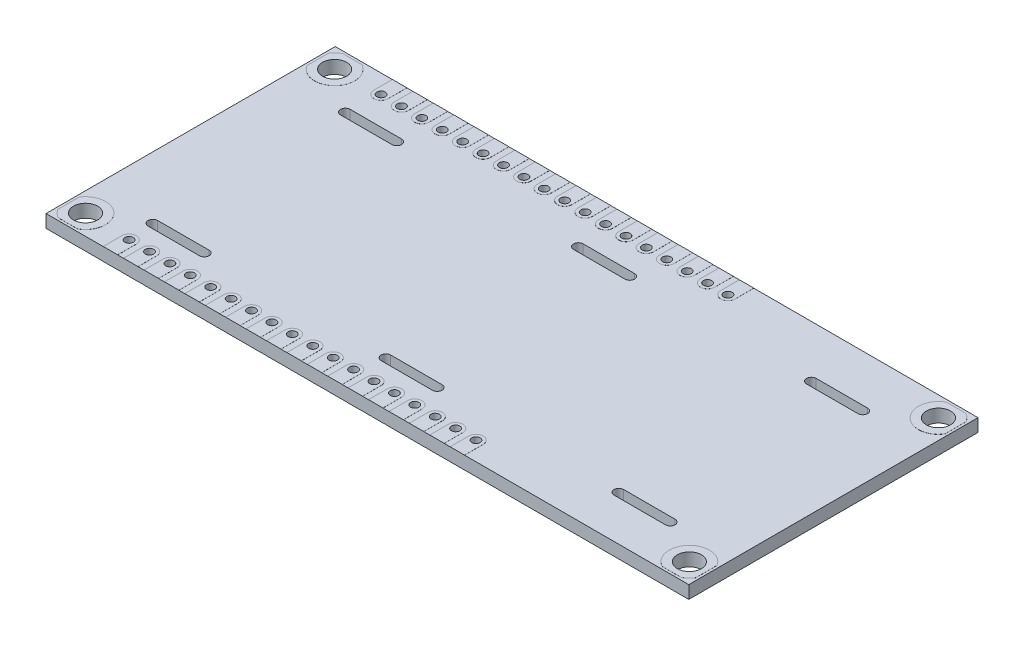
SolidWorks part; units mm, degrees
ref_plane "Plan de face" through (0, 0, 0) normal (0, 0, 1) x (1, 0, 0)
ref_plane "Plan de dessus" through (0, 0, 0) normal (0, 1, 0) x (1, 0, 0)
ref_plane "Plan de droite" through (0, 0, 0) normal (1, 0, 0) x (0, 0, -1)
sketch "Esquisse1" plane through (0, 0, 0) normal (0, 1, 0) x (1, 0, 0)
  line L0 (40, 36) -> (40, 28.6716) construction
  line L1 (0, 0) -> (80, 0)
  line L2 (0, 0) -> (0, 36)
  line L3 (0, 36) -> (80, 36)
  line L4 (80, 0) -> (80, 36)
  line L5 (0, 18) -> (8.7916, 18) construction
  line L6 (-3.0961, 33.68) -> (82.0612, 33.68) construction
  line L7 (7.7, 30.16) -> (14.1, 30.16)
  line L8 (7.7, 6.2) -> (14.1, 6.2)
  line L9 (7.7, 28.96) -> (14.1, 28.96)
  line L10 (7.7, 5) -> (14.1, 5)
  line L11 (36.7, 30.16) -> (43.1, 30.16)
  line L12 (36.7, 28.96) -> (43.1, 28.96)
  line L13 (36.7, 6.2) -> (43.1, 6.2)
  line L14 (36.7, 5) -> (43.1, 5)
  line L15 (65.7, 30.16) -> (72.1, 30.16)
  line L16 (65.7, 28.96) -> (72.1, 28.96)
  line L17 (65.7, 6.2) -> (72.1, 6.2)
  line L18 (65.7, 5) -> (72.1, 5)
  line L19 (72.3, 41.4898) -> (72.3, -1.3318) construction
  circle A0 centre (2.42, 33.5) radius 1.5
  circle A1 centre (2.42, 2.5) radius 1.5
  circle A2 centre (77.58, 2.5) radius 1.5
  circle A3 centre (77.58, 33.5) radius 1.5
  circle A4 centre (8.02, 33.68) radius 0.52
  circle A5 centre (10.56, 33.68) radius 0.52
  circle A6 centre (13.1, 33.68) radius 0.52
  circle A7 centre (15.64, 33.68) radius 0.52
  circle A8 centre (18.18, 33.68) radius 0.52
  circle A9 centre (20.72, 33.68) radius 0.52
  circle A10 centre (23.26, 33.68) radius 0.52
  circle A11 centre (25.8, 33.68) radius 0.52
  circle A12 centre (28.34, 33.68) radius 0.52
  circle A13 centre (30.88, 33.68) radius 0.52
  circle A14 centre (33.42, 33.68) radius 0.52
  circle A15 centre (35.96, 33.68) radius 0.52
  circle A16 centre (38.5, 33.68) radius 0.52
  circle A17 centre (41.04, 33.68) radius 0.52
  circle A18 centre (43.58, 33.68) radius 0.52
  circle A19 centre (46.12, 33.68) radius 0.52
  arc A20 (7.7, 6.2) -> (7.7, 5) centre (7.7, 5.6) ccw
  arc A21 (14.1, 5) -> (14.1, 6.2) centre (14.1, 5.6) ccw
  arc A22 (7.7, 30.16) -> (7.7, 28.96) centre (7.7, 29.56) ccw
  arc A23 (14.1, 28.96) -> (14.1, 30.16) centre (14.1, 29.56) ccw
  arc A24 (36.7, 30.16) -> (36.7, 28.96) centre (36.7, 29.56) ccw
  arc A25 (43.1, 28.96) -> (43.1, 30.16) centre (43.1, 29.56) ccw
  arc A26 (36.7, 6.2) -> (36.7, 5) centre (36.7, 5.6) ccw
  arc A27 (43.1, 5) -> (43.1, 6.2) centre (43.1, 5.6) ccw
  arc A28 (65.7, 30.16) -> (65.7, 28.96) centre (65.7, 29.56) ccw
  arc A29 (72.1, 28.96) -> (72.1, 30.16) centre (72.1, 29.56) ccw
  arc A30 (65.7, 6.2) -> (65.7, 5) centre (65.7, 5.6) ccw
  arc A31 (72.1, 5) -> (72.1, 6.2) centre (72.1, 5.6) ccw
  circle A32 centre (48.66, 33.68) radius 0.52
  circle A33 centre (51.2, 33.68) radius 0.52
  circle A34 centre (51.2, 2.32) radius 0.52
  circle A35 centre (48.66, 2.32) radius 0.52
  circle A36 centre (46.12, 2.32) radius 0.52
  circle A37 centre (41.04, 2.32) radius 0.52
  circle A38 centre (43.58, 2.32) radius 0.52
  circle A39 centre (38.5, 2.32) radius 0.52
  circle A40 centre (35.96, 2.32) radius 0.52
  circle A41 centre (33.42, 2.32) radius 0.52
  circle A42 centre (30.88, 2.32) radius 0.52
  circle A43 centre (28.34, 2.32) radius 0.52
  circle A44 centre (25.8, 2.32) radius 0.52
  circle A45 centre (23.26, 2.32) radius 0.52
  circle A46 centre (20.72, 2.32) radius 0.52
  circle A47 centre (18.18, 2.32) radius 0.52
  circle A48 centre (15.64, 2.32) radius 0.52
  circle A49 centre (13.1, 2.32) radius 0.52
  circle A50 centre (10.56, 2.32) radius 0.52
  circle A51 centre (8.02, 2.32) radius 0.52
  dimension "D3" = 3
  dimension "D8" = 1.04
  dimension "D10" = 1.2
  dimension "D16" = 0.6
  dimension "D18" = 1.04
  dimension "D20" = 1.04
  dimension "D1" = 80
  dimension "D2" = 36
  dimension "D4" = 31
  dimension "D5" = 75.16
  dimension "D6" = 2.32
  dimension "D7" = 8.02
  dimension "D11" = 6.4
  dimension "D12" = 5
  dimension "D13" = 7.7
  dimension "D14" = 5.84
  dimension "D15" = 7.7
  dimension "D17" = 3
  dimension "D19" = 2.54
  dimension "D21" = 2.54
  dimension "D9" = 16
extrude "Boss.-Extru.1" add sketch "Esquisse1" along normal blind 1.6
sketch "Esquisse2" plane through (0, 1.6, 0) normal (0, 1, 0) x (1, 0, 0)
  line L0 (80, 36) -> (0, 36) construction
  line L1 (0.3, 32.175) -> (0.3, 34.825)
  line L2 (7.12, 33.68) -> (7.12, 36)
  line L3 (7.12, 36) -> (8.92, 36)
  line L4 (8.92, 33.68) -> (8.92, 36)
  line L5 (3.6074, 0.3) -> (1.2326, 0.3)
  line L6 (0.3, 1.175) -> (0.3, 3.825)
  line L7 (0, 36) -> (0, 0) construction
  line L8 (0, 0) -> (80, 0) construction
  line L9 (1.2326, 35.7) -> (3.6074, 35.7)
  line L10 (76.3926, 0.3) -> (78.7674, 0.3)
  line L11 (79.7, 1.175) -> (79.7, 3.825)
  line L12 (80, 0) -> (80, 36) construction
  line L13 (79.7, 32.175) -> (79.7, 34.825)
  line L14 (78.7674, 35.7) -> (76.3926, 35.7)
  line L15 (9.66, 33.68) -> (9.66, 36)
  line L16 (9.66, 36) -> (11.46, 36)
  line L17 (11.46, 33.68) -> (11.46, 36)
  line L18 (12.2, 33.68) -> (12.2, 36)
  line L19 (12.2, 36) -> (14, 36)
  line L20 (14, 33.68) -> (14, 36)
  line L21 (14.74, 33.68) -> (14.74, 36)
  line L22 (14.74, 36) -> (16.54, 36)
  line L23 (16.54, 33.68) -> (16.54, 36)
  line L24 (17.28, 33.68) -> (17.28, 36)
  line L25 (17.28, 36) -> (19.08, 36)
  line L26 (19.08, 33.68) -> (19.08, 36)
  line L27 (19.82, 33.68) -> (19.82, 36)
  line L28 (19.82, 36) -> (21.62, 36)
  line L29 (21.62, 33.68) -> (21.62, 36)
  line L30 (22.36, 33.68) -> (22.36, 36)
  line L31 (22.36, 36) -> (24.16, 36)
  line L32 (24.16, 33.68) -> (24.16, 36)
  line L33 (24.9, 33.68) -> (24.9, 36)
  line L34 (24.9, 36) -> (26.7, 36)
  line L35 (26.7, 33.68) -> (26.7, 36)
  line L36 (27.44, 33.68) -> (27.44, 36)
  line L37 (27.44, 36) -> (29.24, 36)
  line L38 (29.24, 33.68) -> (29.24, 36)
  line L39 (29.98, 33.68) -> (29.98, 36)
  line L40 (29.98, 36) -> (31.78, 36)
  line L41 (31.78, 33.68) -> (31.78, 36)
  line L42 (32.52, 33.68) -> (32.52, 36)
  line L43 (32.52, 36) -> (34.32, 36)
  line L44 (34.32, 33.68) -> (34.32, 36)
  line L45 (35.06, 33.68) -> (35.06, 36)
  line L46 (35.06, 36) -> (36.86, 36)
  line L47 (36.86, 33.68) -> (36.86, 36)
  line L48 (37.6, 33.68) -> (37.6, 36)
  line L49 (37.6, 36) -> (39.4, 36)
  line L50 (39.4, 33.68) -> (39.4, 36)
  line L51 (40.14, 33.68) -> (40.14, 36)
  line L52 (40.14, 36) -> (41.94, 36)
  line L53 (41.94, 33.68) -> (41.94, 36)
  line L54 (42.68, 33.68) -> (42.68, 36)
  line L55 (42.68, 36) -> (44.48, 36)
  line L56 (44.48, 33.68) -> (44.48, 36)
  line L57 (45.22, 33.68) -> (45.22, 36)
  line L58 (45.22, 36) -> (47.02, 36)
  line L59 (47.02, 33.68) -> (47.02, 36)
  line L60 (47.76, 33.68) -> (47.76, 36)
  line L61 (47.76, 36) -> (49.56, 36)
  line L62 (49.56, 33.68) -> (49.56, 36)
  line L63 (50.3, 33.68) -> (50.3, 36)
  line L64 (50.3, 36) -> (52.1, 36)
  line L65 (52.1, 33.68) -> (52.1, 36)
  arc A0 (3.6074, 0.3) -> (0.3, 3.825) centre (2.42, 2.5) ccw
  arc A1 (0.3, 32.175) -> (3.6074, 35.7) centre (2.42, 33.5) ccw
  arc A2 (76.3926, 35.7) -> (79.7, 32.175) centre (77.58, 33.5) ccw
  arc A3 (78.7674, 0.3) -> (79.7, 1.175) centre (77.58, 2.5) ccw
  arc A4 (7.12, 33.68) -> (8.92, 33.68) centre (8.02, 33.68) ccw
  circle A5 centre (8.02, 33.68) radius 0.52
  arc A6 (1.2326, 35.7) -> (0.3, 34.825) centre (2.42, 33.5) ccw
  arc A7 (0.3, 1.175) -> (1.2326, 0.3) centre (2.42, 2.5) ccw
  arc A8 (79.7, 3.825) -> (76.3926, 0.3) centre (77.58, 2.5) ccw
  arc A9 (79.7, 34.825) -> (78.7674, 35.7) centre (77.58, 33.5) ccw
  arc A10 (9.66, 33.68) -> (11.46, 33.68) centre (10.56, 33.68) ccw
  circle A11 centre (10.56, 33.68) radius 0.52
  arc A12 (12.2, 33.68) -> (14, 33.68) centre (13.1, 33.68) ccw
  circle A13 centre (13.1, 33.68) radius 0.52
  arc A14 (14.74, 33.68) -> (16.54, 33.68) centre (15.64, 33.68) ccw
  circle A15 centre (15.64, 33.68) radius 0.52
  arc A16 (17.28, 33.68) -> (19.08, 33.68) centre (18.18, 33.68) ccw
  circle A17 centre (18.18, 33.68) radius 0.52
  arc A18 (19.82, 33.68) -> (21.62, 33.68) centre (20.72, 33.68) ccw
  circle A19 centre (20.72, 33.68) radius 0.52
  arc A20 (22.36, 33.68) -> (24.16, 33.68) centre (23.26, 33.68) ccw
  circle A21 centre (23.26, 33.68) radius 0.52
  arc A22 (24.9, 33.68) -> (26.7, 33.68) centre (25.8, 33.68) ccw
  circle A23 centre (25.8, 33.68) radius 0.52
  arc A24 (27.44, 33.68) -> (29.24, 33.68) centre (28.34, 33.68) ccw
  circle A25 centre (28.34, 33.68) radius 0.52
  arc A26 (29.98, 33.68) -> (31.78, 33.68) centre (30.88, 33.68) ccw
  circle A27 centre (30.88, 33.68) radius 0.52
  arc A28 (32.52, 33.68) -> (34.32, 33.68) centre (33.42, 33.68) ccw
  circle A29 centre (33.42, 33.68) radius 0.52
  arc A30 (35.06, 33.68) -> (36.86, 33.68) centre (35.96, 33.68) ccw
  circle A31 centre (35.96, 33.68) radius 0.52
  arc A32 (37.6, 33.68) -> (39.4, 33.68) centre (38.5, 33.68) ccw
  circle A33 centre (38.5, 33.68) radius 0.52
  arc A34 (40.14, 33.68) -> (41.94, 33.68) centre (41.04, 33.68) ccw
  circle A35 centre (41.04, 33.68) radius 0.52
  arc A36 (42.68, 33.68) -> (44.48, 33.68) centre (43.58, 33.68) ccw
  circle A37 centre (43.58, 33.68) radius 0.52
  arc A38 (45.22, 33.68) -> (47.02, 33.68) centre (46.12, 33.68) ccw
  circle A39 centre (46.12, 33.68) radius 0.52
  circle A40 centre (2.42, 33.5) radius 1.5
  circle A41 centre (2.42, 2.5) radius 1.5
  circle A42 centre (77.58, 2.5) radius 1.5
  circle A43 centre (77.58, 33.5) radius 1.5
  arc A44 (47.76, 33.68) -> (49.56, 33.68) centre (48.66, 33.68) ccw
  circle A45 centre (48.66, 33.68) radius 0.52
  circle A46 centre (48.66, 33.68) radius 0.52 construction
  arc A47 (50.3, 33.68) -> (52.1, 33.68) centre (51.2, 33.68) ccw
  circle A48 centre (51.2, 33.68) radius 0.52
  circle A49 centre (51.2, 33.68) radius 0.52 construction
  dimension "D1" = 1.8
  dimension "D2" = 5
  dimension "D5" = 5
  dimension "D8" = 5
  dimension "D11" = 5
  dimension "D3" = 0.3
  dimension "D4" = 0.3
  dimension "D6" = 0.3
  dimension "D7" = 0.3
  dimension "D9" = 0.3
  dimension "D10" = 0.3
  dimension "D12" = 0.3
  dimension "D13" = 0.3
  dimension "D14" = 16
extrude "Boss.-Extru.2" add sketch "Esquisse2" along normal blind 0.01
extrude "Boss.-Extru.3" add sketch "Esquisse2<2>" against normal blind 0.01 from surface starting at face at (10.56, 0, -2.84)
sketch "Esquisse2<2>" plane through (0, 1.6, 0) normal (0, 1, 0) x (1, 0, 0) same geometry as "Esquisse2"
ref_plane "Plan1" through (0, 0, -18) normal (0, 0, -1) x (-1, 0, 0)
sketch "Esquisse3" plane through (0, 0, -18) normal (0, 0, -1) x (-1, 0, 0)
  line L0 (-27.5, 0) -> (-27.5, -12.0338) construction
  line L1 (-27.5, -12.0338) -> (-54, -12.0338) construction
  line L2 (-54, -12.0338) -> (-54, 0) construction
  line L3 (-37.6, 0) -> (-36.86, 0) construction
  line L4 (0, 1.6) -> (0, 0) construction
  line L5 (-62.9183, -1.2) -> (-16.9793, -1.2) construction
  line L6 (-80, 0) -> (-52.1, 0) construction
  line L7 (-67.9847, 0) -> (-4.6388, 0) construction
  line L8 (-59.75, 8.5335) -> (-59.75, -8.5682) construction
  line L9 (-20.75, 7.9666) -> (-20.75, -6.8674) construction
  line L10 (-48.25, 8.5335) -> (-48.25, -15.2765) construction
  line L11 (-34.25, 7.9666) -> (-34.25, -8.5682) construction
  line L12 (-20.75, 0) -> (-27.5, 0)
  line L13 (-27.5, 0) -> (-27.5, -1.2)
  line L14 (-54, 0) -> (-54, -1.2)
  line L15 (-54, 0) -> (-48.25, 0)
  arc A0 (-59.79, 0) -> (-59.75, -0.0173) centre (-54.02, 13.272) ccw
  arc A1 (-27.5, -1.2) -> (-20.75, 0) centre (-27.5, 18.3844) ccw
  arc A2 (-54, -1.2) -> (-48.25, 0) centre (-54.02, 13.272) ccw
  point P2 (0, 0.8)
  point P24 (-59.75, -0.0173)
  point P25 (-48.25, 0)
  point P26 (-54, -1.2)
  point P29 (-34.25, 0)
  point P30 (-20.75, 0)
  point P31 (-27.5, -1.2)
  dimension "D1" = 26.5
  dimension "D2" = 27.5
  dimension "D3" = 1.2
  dimension "D4" = 5.75
  dimension "D5" = 5.75
  dimension "D6" = 6.75
  dimension "D7" = 6.75
revolve "Révolution1" add sketch "Esquisse3" angle 360 about L2 region at (51.8325, -0.4811, -18)
revolve "Révolution2" add sketch "Esquisse3<6>" angle 360 about L0 region at (24.9581, -0.4813, -18)
sketch "Esquisse3<6>" plane through (0, 0, -18) normal (0, 0, -1) x (-1, 0, 0) same geometry as "Esquisse3"
mirror "Mirror1" about plane through (0, 0, -18) normal (0, 0, -1) of "Boss.-Extru.2"
mirror "Mirror2" about plane through (0, 0, -18) normal (0, 0, -1) of "Boss.-Extru.3"
